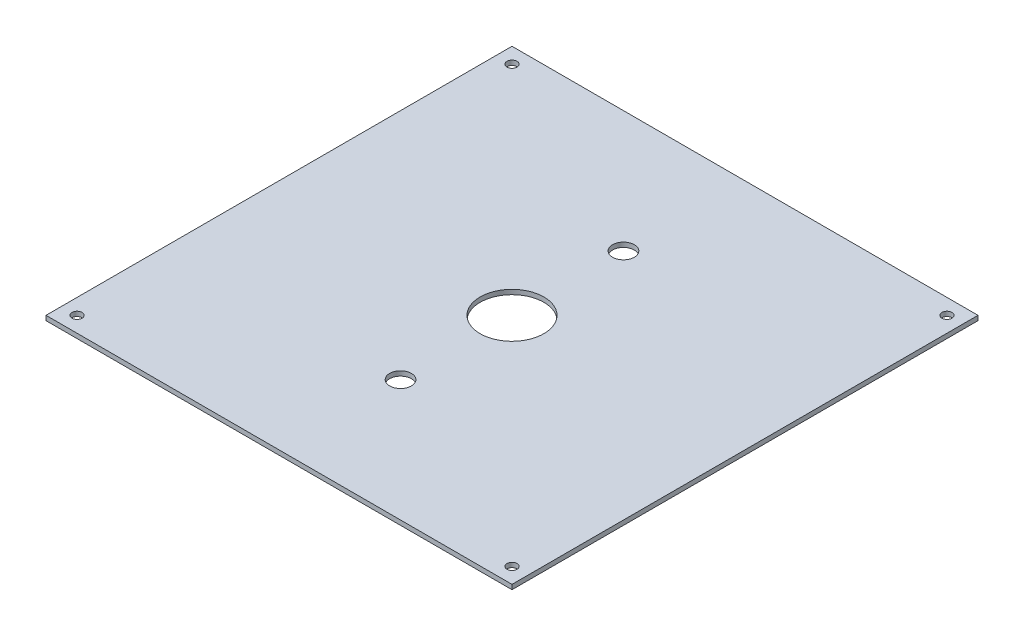
SolidWorks part; units mm, degrees
ref_plane "Front Plane" through (0, 0, 0) normal (0, 0, 1) x (1, 0, 0)
ref_plane "Top Plane" through (0, 0, 0) normal (0, 1, 0) x (1, 0, 0)
ref_plane "Right Plane" through (0, 0, 0) normal (1, 0, 0) x (0, 0, -1)
sketch "Sketch1" plane through (0, 0, 0) normal (0, 1, 0) x (1, 0, 0)
  line L1 (150, 150) -> (-150, 150)
  line L2 (150, 150) -> (150, -150)
  line L3 (150, -150) -> (-150, -150)
  line L4 (-150, 150) -> (-150, -150)
  line L5 (150, 150) -> (-150, -150) construction
  line L6 (150, -150) -> (-150, 150) construction
  point P0 (0, 0)
  dimension "D1" = 300
extrude "Boss-Extrude1" add sketch "Sketch1" along normal blind 3
sketch "Sketch2" plane through (0, 3, 0) normal (0, 1, 0) x (1, 0, 0)
  line L0 (-150, 150) -> (150, -150) construction
  line L1 (-150, 0) -> (150, 0) construction
  line L2 (-150, 150) -> (-150, -150) construction
  line L3 (150, -150) -> (150, 150) construction
  line L4 (0, 150) -> (0, -150) construction
  line L5 (150, 150) -> (-150, 150) construction
  line L6 (-150, -150) -> (150, -150) construction
  circle A0 centre (-140, 140) radius 3.25
  circle A1 centre (140, 140) radius 3.25
  circle A2 centre (140, -140) radius 3.25
  circle A3 centre (-140, -140) radius 3.25
  dimension "D1" = 6.5
  dimension "D2" = 280
extrude "Cut-Extrude1" cut sketch "Sketch2" against normal up to next
sketch "Sketch3" plane through (0, 3, 0) normal (0, 1, 0) x (1, 0, 0)
  circle A0 centre (0, 0) radius 20.5
  dimension "D1" = 41
extrude "Cut-Extrude2" cut sketch "Sketch3" against normal up to next
sketch "Sketch4" plane through (0, 3, 0) normal (0, 1, 0) x (1, 0, 0)
  line L0 (0, 150) -> (0, -150) construction
  line L1 (150, 150) -> (-150, 150) construction
  line L2 (-150, -150) -> (150, -150) construction
  line L3 (-150, 0) -> (150, 0) construction
  line L4 (-150, 150) -> (-150, -150) construction
  line L5 (150, -150) -> (150, 150) construction
  circle A0 centre (0, 71.75) radius 7
  circle A1 centre (0, -71.75) radius 7
  dimension "D1" = 14
  dimension "D2" = 143.5
extrude "Cut-Extrude3" cut sketch "Sketch4" against normal up to next
